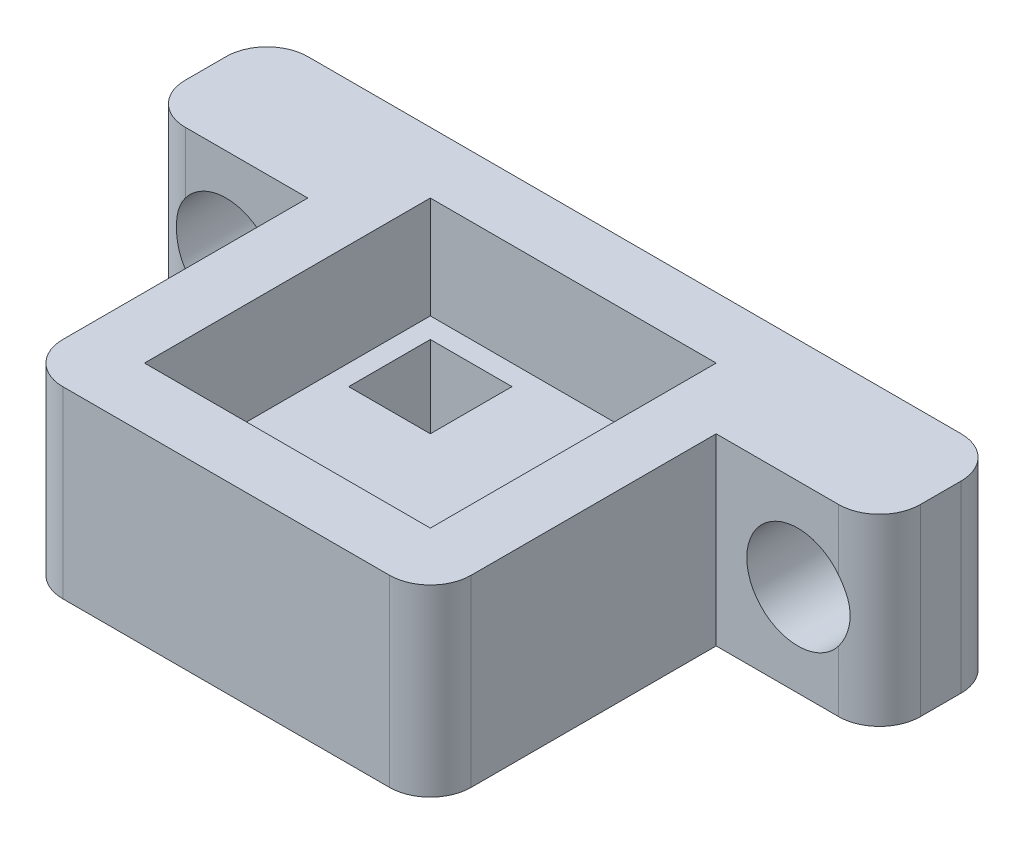
SolidWorks part; units mm, degrees
ref_plane "Front" through (0, 0, 0) normal (0, 0, 1) x (1, 0, 0)
ref_plane "Top" through (0, 0, 0) normal (0, 1, 0) x (1, 0, 0)
ref_plane "Right" through (0, 0, 0) normal (1, 0, 0) x (0, 0, -1)
sketch "Esboço1" plane through (0, 0, 0) normal (0, 1, 0) x (1, 0, 0)
  line L0 (3, 3) -> (1, 3)
  line L1 (5, 5) -> (-5, 5)
  line L2 (5, 5) -> (5, -5)
  line L3 (5, -5) -> (-5, -5)
  line L4 (-5, 5) -> (-5, -5)
  line L5 (0, -3) -> (0, -1) construction
  line L7 (-3, 3) -> (-3, 1)
  line L8 (3, -3) -> (1, -3)
  line L9 (3, 3) -> (3, 1)
  line L10 (3, 1) -> (1, 1)
  line L11 (3, -1) -> (1, -1)
  line L15 (-3, -1) -> (-3, -3)
  line L16 (-3, 3) -> (-3, -3) construction
  line L17 (3, -1) -> (3, -3)
  line L18 (3, 3) -> (3, -3) construction
  line L19 (1, -3) -> (1, -1)
  line L20 (-1, -3) -> (-1, -1)
  line L21 (1, -5) -> (1, 5) construction
  line L22 (0, -5) -> (0, 5) construction
  line L23 (-1, -5) -> (-1, 5) construction
  line L24 (-1, -3) -> (-3, -3)
  line L25 (3, -3) -> (-3, -3) construction
  line L26 (0, 0) -> (-3, 0) construction
  line L27 (-1, 1) -> (-3, 1)
  line L28 (-1, 3) -> (-3, 3)
  line L29 (3, 3) -> (-3, 3) construction
  line L30 (-1, -1) -> (-3, -1)
  line L31 (-1, 1) -> (-1, 3)
  line L33 (1, 1) -> (1, 3)
  point P0 (0, 0)
  dimension "D1" = 2
  dimension "D4" = 1
  dimension "D5" = 1
extrude "Ressalto-extrusão1" add sketch "Esboço1" along normal blind 2
sketch "Esboço2" plane through (0, 2, 0) normal (0, 1, 0) x (1, 0, 0)
  line L0 (3, -3) -> (3, -1) construction
  line L1 (1, -3) -> (3, -3) construction
  line L2 (-3, -3) -> (-1, -3) construction
  line L3 (-3, -1) -> (-3, -3) construction
  line L4 (-3, 3) -> (-3, 1) construction
  line L5 (-1, 3) -> (-3, 3) construction
  line L6 (3, 3) -> (1, 3) construction
  line L7 (3, 1) -> (3, 3) construction
  line L8 (-5, -5) -> (5, -5) construction
  line L9 (5, -5) -> (5, 5) construction
  line L10 (5, 5) -> (-5, 5) construction
  line L11 (-5, 5) -> (-5, -5) construction
  line L12 (3, -3) -> (3, -1)
  line L13 (-1, -3) -> (3, -3)
  line L14 (-3, -3) -> (-1, -3)
  line L15 (-3, 1) -> (-3, -3)
  line L16 (-3, 3) -> (-3, 1)
  line L17 (1, 3) -> (-3, 3)
  line L18 (3, 3) -> (1, 3)
  line L19 (3, -3) -> (3, 3)
  line L20 (-5, -5) -> (5, -5)
  line L21 (5, -5) -> (5, 5)
  line L22 (5, 5) -> (-5, 5)
  line L23 (-5, 5) -> (-5, -5)
  line L24 (3.5, -3.5) -> (3.5, 3.5)
  line L25 (3.5, 3.5) -> (1, 3.5)
  line L26 (1, 3.5) -> (-3.5, 3.5)
  line L27 (-3.5, 3.5) -> (-3.5, 1)
  line L28 (-3.5, 1) -> (-3.5, -3.5)
  line L29 (-3.5, -3.5) -> (-1, -3.5)
  line L30 (-1, -3.5) -> (3.5, -3.5)
  line M21 (-5, 5) -> (-5, -5)
  line M22 (-5, -5) -> (5, -5)
  line M23 (5, -5) -> (5, 5)
  line M24 (5, 5) -> (-5, 5)
  dimension "D1" = 0.5
extrude "Ressalto-extrusão2" add sketch "Esboço2" along normal blind 2.5 contours L30 L29 L28 L27 L26 L25 L24 M24 M21 M22 M23 region at (-4.8586, 2, 0)
sketch "Esboço3" plane through (0, 0, -5) normal (0, 0, -1) x (-1, 0, 0)
  line L0 (-7, 2.25) -> (7, 2.25) construction
  line L2 (-5, 4.5) -> (-5, 0) construction
  line L3 (5, 4.5) -> (5, 0) construction
  line L4 (5, 4.5) -> (5, 0)
  line L5 (-5, 4.5) -> (-5, 0)
  line L6 (0, 2.25) -> (0, 6.1582) construction
  line L7 (-5, 4.5) -> (-9, 4.5)
  line L8 (-5, 4.5) -> (-5, 0)
  line L9 (-5, 0) -> (-9, 0)
  line L10 (-9, 4.5) -> (-9, 0)
  line L11 (9, 4.5) -> (9, 0)
  line L12 (5, 0) -> (9, 0)
  line L13 (5, 4.5) -> (5, 0)
  line L14 (5, 4.5) -> (9, 4.5)
  circle A0 centre (-7, 2.25) radius 1.25
  circle A1 centre (7, 2.25) radius 1.25
  point P4 (-5, 2.25)
  line M10 (5, 0) -> (5, 4.5)
  line M12 (-5, 4.5) -> (-5, 0)
  dimension "D3" = 4
  dimension "D4" = 2.5
  dimension "D1" = 2
  dimension "D2" = 2
extrude "Ressalto-extrusão3" add sketch "Esboço3" against normal blind 3 contours L7 L10 L9 A0 M12 | L14 L12 L11 A1 M10 region at (-7, 4.4398, -5) region at (5.0602, 2.25, -5)
fillet "Filete1" radius 1 6 edges at (-9, 2.25, -2) (-9, 2.25, -5) (9, 2.25, -5) (9, 2.25, -2) (5, 2.25, 5) (-5, 2.25, 5)
